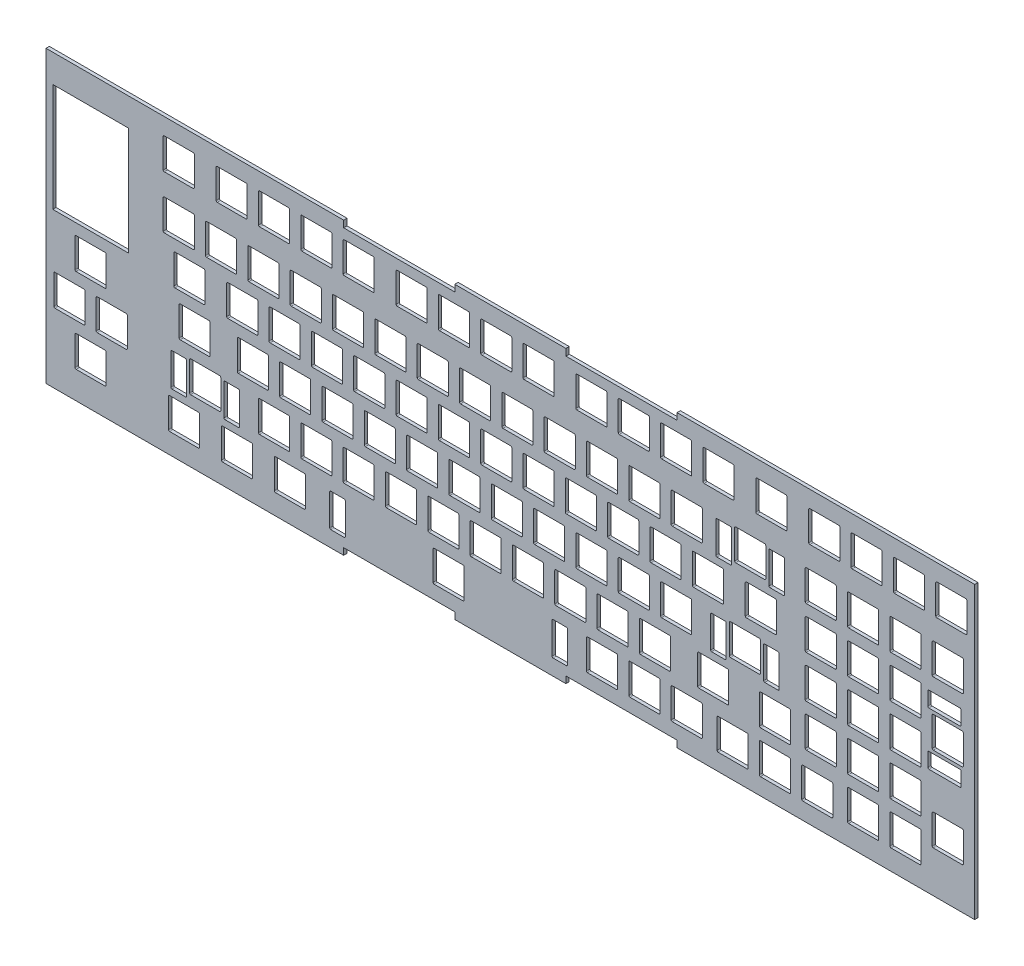
SolidWorks part; units mm, degrees
ref_plane "Přední rovina" through (0, 0, 0) normal (0, 0, 1) x (1, 0, 0)
ref_plane "Horní rovina" through (0, 0, 0) normal (0, 1, 0) x (1, 0, 0)
ref_plane "Pravá rovina" through (0, 0, 0) normal (1, 0, 0) x (0, 0, -1)
sketch "Model" plane through (0, 0, 0) normal (0, 0, 1) x (1, 0, 0)
  line L0 (53.8256, -2.525) -> (66.8256, -2.525)
  line L1 (53.8256, -16.525) -> (66.8256, -16.525)
  line L2 (53.3256, -3.025) -> (53.3256, -16.025)
  line L3 (67.3256, -3.025) -> (67.3256, -16.025)
  line L4 (77.6381, -2.525) -> (90.6381, -2.525)
  line L5 (77.6381, -16.525) -> (90.6381, -16.525)
  line L6 (77.1381, -3.025) -> (77.1381, -16.025)
  line L7 (91.1381, -3.025) -> (91.1381, -16.025)
  line L8 (96.6881, -2.525) -> (109.6881, -2.525)
  line L9 (96.6881, -16.525) -> (109.6881, -16.525)
  line L10 (96.1881, -3.025) -> (96.1881, -16.025)
  line L11 (110.1881, -3.025) -> (110.1881, -16.025)
  line L12 (115.7381, -2.525) -> (128.7381, -2.525)
  line L13 (115.7381, -16.525) -> (128.7381, -16.525)
  line L14 (115.2381, -3.025) -> (115.2381, -16.025)
  line L15 (129.2381, -3.025) -> (129.2381, -16.025)
  line L16 (134.7881, -2.525) -> (147.7881, -2.525)
  line L17 (134.7881, -16.525) -> (147.7881, -16.525)
  line L18 (134.2881, -3.025) -> (134.2881, -16.025)
  line L19 (148.2881, -3.025) -> (148.2881, -16.025)
  line L20 (158.6006, -2.525) -> (171.6006, -2.525)
  line L21 (158.6006, -16.525) -> (171.6006, -16.525)
  line L22 (158.1006, -3.025) -> (158.1006, -16.025)
  line L23 (172.1006, -3.025) -> (172.1006, -16.025)
  line L24 (177.6506, -2.525) -> (190.6506, -2.525)
  line L25 (177.6506, -16.525) -> (190.6506, -16.525)
  line L26 (177.1506, -3.025) -> (177.1506, -16.025)
  line L27 (191.1506, -3.025) -> (191.1506, -16.025)
  line L28 (196.7006, -2.525) -> (209.7006, -2.525)
  line L29 (196.7006, -16.525) -> (209.7006, -16.525)
  line L30 (196.2006, -3.025) -> (196.2006, -16.025)
  line L31 (210.2006, -3.025) -> (210.2006, -16.025)
  line L32 (215.7506, -2.525) -> (228.7506, -2.525)
  line L33 (215.7506, -16.525) -> (228.7506, -16.525)
  line L34 (215.2506, -3.025) -> (215.2506, -16.025)
  line L35 (229.2506, -3.025) -> (229.2506, -16.025)
  line L36 (239.5631, -2.525) -> (252.5631, -2.525)
  line L37 (239.5631, -16.525) -> (252.5631, -16.525)
  line L38 (239.0631, -3.025) -> (239.0631, -16.025)
  line L39 (253.0631, -3.025) -> (253.0631, -16.025)
  line L40 (258.6131, -2.525) -> (271.6131, -2.525)
  line L41 (258.6131, -16.525) -> (271.6131, -16.525)
  line L42 (258.1131, -3.025) -> (258.1131, -16.025)
  line L43 (272.1131, -3.025) -> (272.1131, -16.025)
  line L44 (277.6631, -2.525) -> (290.6631, -2.525)
  line L45 (277.6631, -16.525) -> (290.6631, -16.525)
  line L46 (277.1631, -3.025) -> (277.1631, -16.025)
  line L47 (291.1631, -3.025) -> (291.1631, -16.025)
  line L48 (296.7131, -2.525) -> (309.7131, -2.525)
  line L49 (296.7131, -16.525) -> (309.7131, -16.525)
  line L50 (296.2131, -3.025) -> (296.2131, -16.025)
  line L51 (310.2131, -3.025) -> (310.2131, -16.025)
  line L52 (320.5256, -2.525) -> (333.5256, -2.525)
  line L53 (320.5256, -16.525) -> (333.5256, -16.525)
  line L54 (320.0256, -3.025) -> (320.0256, -16.025)
  line L55 (334.0256, -3.025) -> (334.0256, -16.025)
  line L56 (344.3381, -2.525) -> (357.3381, -2.525)
  line L57 (344.3381, -16.525) -> (357.3381, -16.525)
  line L58 (343.8381, -3.025) -> (343.8381, -16.025)
  line L59 (357.8381, -3.025) -> (357.8381, -16.025)
  line L60 (363.3881, -2.525) -> (376.3881, -2.525)
  line L61 (363.3881, -16.525) -> (376.3881, -16.525)
  line L62 (362.8881, -3.025) -> (362.8881, -16.025)
  line L63 (376.8881, -3.025) -> (376.8881, -16.025)
  line L64 (382.4381, -2.525) -> (395.4381, -2.525)
  line L65 (382.4381, -16.525) -> (395.4381, -16.525)
  line L66 (381.9381, -3.025) -> (381.9381, -16.025)
  line L67 (395.9381, -3.025) -> (395.9381, -16.025)
  line L68 (401.4881, -2.525) -> (414.4881, -2.525)
  line L69 (401.4881, -16.525) -> (414.4881, -16.525)
  line L70 (400.9881, -3.025) -> (400.9881, -16.025)
  line L71 (414.9881, -3.025) -> (414.9881, -16.025)
  line L72 (53.8256, -26.3375) -> (66.8256, -26.3375)
  line L73 (53.8256, -40.3375) -> (66.8256, -40.3375)
  line L74 (53.3256, -26.8375) -> (53.3256, -39.8375)
  line L75 (67.3256, -26.8375) -> (67.3256, -39.8375)
  line L76 (72.8756, -26.3375) -> (85.8756, -26.3375)
  line L77 (72.8756, -40.3375) -> (85.8756, -40.3375)
  line L78 (72.3756, -26.8375) -> (72.3756, -39.8375)
  line L79 (86.3756, -26.8375) -> (86.3756, -39.8375)
  line L80 (91.9256, -26.3375) -> (104.9256, -26.3375)
  line L81 (91.9256, -40.3375) -> (104.9256, -40.3375)
  line L82 (91.4256, -26.8375) -> (91.4256, -39.8375)
  line L83 (105.4256, -26.8375) -> (105.4256, -39.8375)
  line L84 (110.9756, -26.3375) -> (123.9756, -26.3375)
  line L85 (110.9756, -40.3375) -> (123.9756, -40.3375)
  line L86 (110.4756, -26.8375) -> (110.4756, -39.8375)
  line L87 (124.4756, -26.8375) -> (124.4756, -39.8375)
  line L88 (130.0256, -26.3375) -> (143.0256, -26.3375)
  line L89 (130.0256, -40.3375) -> (143.0256, -40.3375)
  line L90 (129.5256, -26.8375) -> (129.5256, -39.8375)
  line L91 (143.5256, -26.8375) -> (143.5256, -39.8375)
  line L92 (149.0756, -26.3375) -> (162.0756, -26.3375)
  line L93 (149.0756, -40.3375) -> (162.0756, -40.3375)
  line L94 (148.5756, -26.8375) -> (148.5756, -39.8375)
  line L95 (162.5756, -26.8375) -> (162.5756, -39.8375)
  line L96 (168.1256, -26.3375) -> (181.1256, -26.3375)
  line L97 (168.1256, -40.3375) -> (181.1256, -40.3375)
  line L98 (167.6256, -26.8375) -> (167.6256, -39.8375)
  line L99 (181.6256, -26.8375) -> (181.6256, -39.8375)
  line L100 (187.1756, -26.3375) -> (200.1756, -26.3375)
  line L101 (187.1756, -40.3375) -> (200.1756, -40.3375)
  line L102 (186.6756, -26.8375) -> (186.6756, -39.8375)
  line L103 (200.6756, -26.8375) -> (200.6756, -39.8375)
  line L104 (206.2256, -26.3375) -> (219.2256, -26.3375)
  line L105 (206.2256, -40.3375) -> (219.2256, -40.3375)
  line L106 (205.7256, -26.8375) -> (205.7256, -39.8375)
  line L107 (219.7256, -26.8375) -> (219.7256, -39.8375)
  line L108 (225.2756, -26.3375) -> (238.2756, -26.3375)
  line L109 (225.2756, -40.3375) -> (238.2756, -40.3375)
  line L110 (224.7756, -26.8375) -> (224.7756, -39.8375)
  line L111 (238.7756, -26.8375) -> (238.7756, -39.8375)
  line L112 (244.3256, -26.3375) -> (257.3256, -26.3375)
  line L113 (244.3256, -40.3375) -> (257.3256, -40.3375)
  line L114 (243.8256, -26.8375) -> (243.8256, -39.8375)
  line L115 (257.8256, -26.8375) -> (257.8256, -39.8375)
  line L116 (263.3756, -26.3375) -> (276.3756, -26.3375)
  line L117 (263.3756, -40.3375) -> (276.3756, -40.3375)
  line L118 (262.8756, -26.8375) -> (262.8756, -39.8375)
  line L119 (276.8756, -26.8375) -> (276.8756, -39.8375)
  line L120 (282.4256, -26.3375) -> (295.4256, -26.3375)
  line L121 (282.4256, -40.3375) -> (295.4256, -40.3375)
  line L122 (281.9256, -26.8375) -> (281.9256, -39.8375)
  line L123 (295.9256, -26.8375) -> (295.9256, -39.8375)
  line L124 (311.0006, -26.3375) -> (324.0006, -26.3375)
  line L125 (311.0006, -40.3375) -> (324.0006, -40.3375)
  line L126 (310.5006, -26.8375) -> (310.5006, -39.8375)
  line L127 (324.5006, -26.8375) -> (324.5006, -39.8375)
  line L128 (302.5626, -27.3375) -> (308.5626, -27.3375)
  line L129 (302.5626, -42.3375) -> (308.5626, -42.3375)
  line L130 (302.0626, -27.8375) -> (302.0626, -41.8375)
  line L131 (309.0626, -27.8375) -> (309.0626, -41.8375)
  line L132 (326.4386, -27.3375) -> (332.4386, -27.3375)
  line L133 (326.4386, -42.3375) -> (332.4386, -42.3375)
  line L134 (325.9386, -27.8375) -> (325.9386, -41.8375)
  line L135 (332.9386, -27.8375) -> (332.9386, -41.8375)
  line L136 (342.7513, -26.3375) -> (355.7513, -26.3375)
  line L137 (342.7513, -40.3375) -> (355.7513, -40.3375)
  line L138 (342.2513, -26.8375) -> (342.2513, -39.8375)
  line L139 (356.2513, -26.8375) -> (356.2513, -39.8375)
  line L140 (361.8013, -26.3375) -> (374.8013, -26.3375)
  line L141 (361.8013, -40.3375) -> (374.8013, -40.3375)
  line L142 (361.3013, -26.8375) -> (361.3013, -39.8375)
  line L143 (375.3013, -26.8375) -> (375.3013, -39.8375)
  line L144 (380.8513, -26.3375) -> (393.8513, -26.3375)
  line L145 (380.8513, -40.3375) -> (393.8513, -40.3375)
  line L146 (380.3513, -26.8375) -> (380.3513, -39.8375)
  line L147 (394.3513, -26.8375) -> (394.3513, -39.8375)
  line L148 (399.9013, -26.3375) -> (412.9013, -26.3375)
  line L149 (399.9013, -40.3375) -> (412.9013, -40.3375)
  line L150 (399.4013, -26.8375) -> (399.4013, -39.8375)
  line L151 (413.4013, -26.8375) -> (413.4013, -39.8375)
  line L152 (58.5881, -45.3875) -> (71.5881, -45.3875)
  line L153 (58.5881, -59.3875) -> (71.5881, -59.3875)
  line L154 (58.0881, -45.8875) -> (58.0881, -58.8875)
  line L155 (72.0881, -45.8875) -> (72.0881, -58.8875)
  line L156 (82.4006, -45.3875) -> (95.4006, -45.3875)
  line L157 (82.4006, -59.3875) -> (95.4006, -59.3875)
  line L158 (81.9006, -45.8875) -> (81.9006, -58.8875)
  line L159 (95.9006, -45.8875) -> (95.9006, -58.8875)
  line L160 (101.4506, -45.3875) -> (114.4506, -45.3875)
  line L161 (101.4506, -59.3875) -> (114.4506, -59.3875)
  line L162 (100.9506, -45.8875) -> (100.9506, -58.8875)
  line L163 (114.9506, -45.8875) -> (114.9506, -58.8875)
  line L164 (120.5006, -45.3875) -> (133.5006, -45.3875)
  line L165 (120.5006, -59.3875) -> (133.5006, -59.3875)
  line L166 (120.0006, -45.8875) -> (120.0006, -58.8875)
  line L167 (134.0006, -45.8875) -> (134.0006, -58.8875)
  line L168 (139.5506, -45.3875) -> (152.5506, -45.3875)
  line L169 (139.5506, -59.3875) -> (152.5506, -59.3875)
  line L170 (139.0506, -45.8875) -> (139.0506, -58.8875)
  line L171 (153.0506, -45.8875) -> (153.0506, -58.8875)
  line L172 (158.6006, -45.3875) -> (171.6006, -45.3875)
  line L173 (158.6006, -59.3875) -> (171.6006, -59.3875)
  line L174 (158.1006, -45.8875) -> (158.1006, -58.8875)
  line L175 (172.1006, -45.8875) -> (172.1006, -58.8875)
  line L176 (177.6506, -45.3875) -> (190.6506, -45.3875)
  line L177 (177.6506, -59.3875) -> (190.6506, -59.3875)
  line L178 (177.1506, -45.8875) -> (177.1506, -58.8875)
  line L179 (191.1506, -45.8875) -> (191.1506, -58.8875)
  line L180 (196.7006, -45.3875) -> (209.7006, -45.3875)
  line L181 (196.7006, -59.3875) -> (209.7006, -59.3875)
  line L182 (196.2006, -45.8875) -> (196.2006, -58.8875)
  line L183 (210.2006, -45.8875) -> (210.2006, -58.8875)
  line L184 (215.7506, -45.3875) -> (228.7506, -45.3875)
  line L185 (215.7506, -59.3875) -> (228.7506, -59.3875)
  line L186 (215.2506, -45.8875) -> (215.2506, -58.8875)
  line L187 (229.2506, -45.8875) -> (229.2506, -58.8875)
  line L188 (234.8006, -45.3875) -> (247.8006, -45.3875)
  line L189 (234.8006, -59.3875) -> (247.8006, -59.3875)
  line L190 (234.3006, -45.8875) -> (234.3006, -58.8875)
  line L191 (248.3006, -45.8875) -> (248.3006, -58.8875)
  line L192 (253.8506, -45.3875) -> (266.8506, -45.3875)
  line L193 (253.8506, -59.3875) -> (266.8506, -59.3875)
  line L194 (253.3506, -45.8875) -> (253.3506, -58.8875)
  line L195 (267.3506, -45.8875) -> (267.3506, -58.8875)
  line L196 (272.9006, -45.3875) -> (285.9006, -45.3875)
  line L197 (272.9006, -59.3875) -> (285.9006, -59.3875)
  line L198 (272.4006, -45.8875) -> (272.4006, -58.8875)
  line L199 (286.4006, -45.8875) -> (286.4006, -58.8875)
  line L200 (291.9506, -45.3875) -> (304.9506, -45.3875)
  line L201 (291.9506, -59.3875) -> (304.9506, -59.3875)
  line L202 (291.4506, -45.8875) -> (291.4506, -58.8875)
  line L203 (305.4506, -45.8875) -> (305.4506, -58.8875)
  line L204 (315.7631, -45.3875) -> (328.7631, -45.3875)
  line L205 (315.7631, -59.3875) -> (328.7631, -59.3875)
  line L206 (315.2631, -45.8875) -> (315.2631, -58.8875)
  line L207 (329.2631, -45.8875) -> (329.2631, -58.8875)
  line L208 (342.7513, -45.3875) -> (355.7513, -45.3875)
  line L209 (342.7513, -59.3875) -> (355.7513, -59.3875)
  line L210 (342.2513, -45.8875) -> (342.2513, -58.8875)
  line L211 (356.2513, -45.8875) -> (356.2513, -58.8875)
  line L212 (361.8013, -45.3875) -> (374.8013, -45.3875)
  line L213 (361.8013, -59.3875) -> (374.8013, -59.3875)
  line L214 (361.3013, -45.8875) -> (361.3013, -58.8875)
  line L215 (375.3013, -45.8875) -> (375.3013, -58.8875)
  line L216 (380.8513, -45.3875) -> (393.8513, -45.3875)
  line L217 (380.8513, -59.3875) -> (393.8513, -59.3875)
  line L218 (380.3513, -45.8875) -> (380.3513, -58.8875)
  line L219 (394.3513, -45.8875) -> (394.3513, -58.8875)
  line L220 (413.4013, -55.4125) -> (413.4013, -68.4125)
  line L221 (399.4013, -55.4125) -> (399.4013, -68.4125)
  line L222 (412.9013, -54.9125) -> (399.9013, -54.9125)
  line L223 (412.9013, -68.9125) -> (399.9013, -68.9125)
  line L224 (412.4013, -46.9745) -> (412.4013, -52.9745)
  line L225 (397.4013, -46.9745) -> (397.4013, -52.9745)
  line L226 (411.9013, -46.4745) -> (397.9013, -46.4745)
  line L227 (411.9013, -53.4745) -> (397.9013, -53.4745)
  line L228 (412.4013, -70.8505) -> (412.4013, -76.8505)
  line L229 (397.4013, -70.8505) -> (397.4013, -76.8505)
  line L230 (411.9013, -70.3505) -> (397.9013, -70.3505)
  line L231 (411.9013, -77.3505) -> (397.9013, -77.3505)
  line L232 (14.1369, -61.2619) -> (27.1369, -61.2619)
  line L233 (14.1369, -75.2619) -> (27.1369, -75.2619)
  line L234 (13.6369, -61.7619) -> (13.6369, -74.7619)
  line L235 (27.6369, -61.7619) -> (27.6369, -74.7619)
  line L236 (60.9694, -64.4375) -> (73.9694, -64.4375)
  line L237 (60.9694, -78.4375) -> (73.9694, -78.4375)
  line L238 (60.4694, -64.9375) -> (60.4694, -77.9375)
  line L239 (74.4694, -64.9375) -> (74.4694, -77.9375)
  line L240 (87.1631, -64.4375) -> (100.1631, -64.4375)
  line L241 (87.1631, -78.4375) -> (100.1631, -78.4375)
  line L242 (86.6631, -64.9375) -> (86.6631, -77.9375)
  line L243 (100.6631, -64.9375) -> (100.6631, -77.9375)
  line L244 (106.2131, -64.4375) -> (119.2131, -64.4375)
  line L245 (106.2131, -78.4375) -> (119.2131, -78.4375)
  line L246 (105.7131, -64.9375) -> (105.7131, -77.9375)
  line L247 (119.7131, -64.9375) -> (119.7131, -77.9375)
  line L248 (125.2631, -64.4375) -> (138.2631, -64.4375)
  line L249 (125.2631, -78.4375) -> (138.2631, -78.4375)
  line L250 (124.7631, -64.9375) -> (124.7631, -77.9375)
  line L251 (138.7631, -64.9375) -> (138.7631, -77.9375)
  line L252 (144.3131, -64.4375) -> (157.3131, -64.4375)
  line L253 (144.3131, -78.4375) -> (157.3131, -78.4375)
  line L254 (143.8131, -64.9375) -> (143.8131, -77.9375)
  line L255 (157.8131, -64.9375) -> (157.8131, -77.9375)
  line L256 (163.3631, -64.4375) -> (176.3631, -64.4375)
  line L257 (163.3631, -78.4375) -> (176.3631, -78.4375)
  line L258 (162.8631, -64.9375) -> (162.8631, -77.9375)
  line L259 (176.8631, -64.9375) -> (176.8631, -77.9375)
  line L260 (182.4131, -64.4375) -> (195.4131, -64.4375)
  line L261 (182.4131, -78.4375) -> (195.4131, -78.4375)
  line L262 (181.9131, -64.9375) -> (181.9131, -77.9375)
  line L263 (195.9131, -64.9375) -> (195.9131, -77.9375)
  line L264 (201.4631, -64.4375) -> (214.4631, -64.4375)
  line L265 (201.4631, -78.4375) -> (214.4631, -78.4375)
  line L266 (200.9631, -64.9375) -> (200.9631, -77.9375)
  line L267 (214.9631, -64.9375) -> (214.9631, -77.9375)
  line L268 (220.5131, -64.4375) -> (233.5131, -64.4375)
  line L269 (220.5131, -78.4375) -> (233.5131, -78.4375)
  line L270 (220.0131, -64.9375) -> (220.0131, -77.9375)
  line L271 (234.0131, -64.9375) -> (234.0131, -77.9375)
  line L272 (239.5631, -64.4375) -> (252.5631, -64.4375)
  line L273 (239.5631, -78.4375) -> (252.5631, -78.4375)
  line L274 (239.0631, -64.9375) -> (239.0631, -77.9375)
  line L275 (253.0631, -64.9375) -> (253.0631, -77.9375)
  line L276 (258.6131, -64.4375) -> (271.6131, -64.4375)
  line L277 (258.6131, -78.4375) -> (271.6131, -78.4375)
  line L278 (258.1131, -64.9375) -> (258.1131, -77.9375)
  line L279 (272.1131, -64.9375) -> (272.1131, -77.9375)
  line L280 (277.6631, -64.4375) -> (290.6631, -64.4375)
  line L281 (277.6631, -78.4375) -> (290.6631, -78.4375)
  line L282 (277.1631, -64.9375) -> (277.1631, -77.9375)
  line L283 (291.1631, -64.9375) -> (291.1631, -77.9375)
  line L284 (308.6194, -64.4375) -> (321.6194, -64.4375)
  line L285 (308.6194, -78.4375) -> (321.6194, -78.4375)
  line L286 (308.1194, -64.9375) -> (308.1194, -77.9375)
  line L287 (322.1194, -64.9375) -> (322.1194, -77.9375)
  line L288 (300.1814, -65.4375) -> (306.1814, -65.4375)
  line L289 (300.1814, -80.4375) -> (306.1814, -80.4375)
  line L290 (299.6814, -65.9375) -> (299.6814, -79.9375)
  line L291 (306.6814, -65.9375) -> (306.6814, -79.9375)
  line L292 (324.0574, -65.4375) -> (330.0574, -65.4375)
  line L293 (324.0574, -80.4375) -> (330.0574, -80.4375)
  line L294 (323.5574, -65.9375) -> (323.5574, -79.9375)
  line L295 (330.5574, -65.9375) -> (330.5574, -79.9375)
  line L296 (342.7513, -64.4375) -> (355.7513, -64.4375)
  line L297 (342.7513, -78.4375) -> (355.7513, -78.4375)
  line L298 (342.2513, -64.9375) -> (342.2513, -77.9375)
  line L299 (356.2513, -64.9375) -> (356.2513, -77.9375)
  line L300 (361.8013, -64.4375) -> (374.8013, -64.4375)
  line L301 (361.8013, -78.4375) -> (374.8013, -78.4375)
  line L302 (361.3013, -64.9375) -> (361.3013, -77.9375)
  line L303 (375.3013, -64.9375) -> (375.3013, -77.9375)
  line L304 (380.8513, -64.4375) -> (393.8513, -64.4375)
  line L305 (380.8513, -78.4375) -> (393.8513, -78.4375)
  line L306 (380.3513, -64.9375) -> (380.3513, -77.9375)
  line L307 (394.3513, -64.9375) -> (394.3513, -77.9375)
  line L308 (4.6119, -80.3119) -> (17.6119, -80.3119)
  line L309 (4.6119, -94.3119) -> (17.6119, -94.3119)
  line L310 (4.1119, -80.8119) -> (4.1119, -93.8119)
  line L311 (18.1119, -80.8119) -> (18.1119, -93.8119)
  line L312 (23.6619, -80.3119) -> (36.6619, -80.3119)
  line L313 (23.6619, -94.3119) -> (36.6619, -94.3119)
  line L314 (23.1619, -80.8119) -> (23.1619, -93.8119)
  line L315 (37.1619, -80.8119) -> (37.1619, -93.8119)
  line L316 (65.7319, -83.4875) -> (78.7319, -83.4875)
  line L317 (65.7319, -97.4875) -> (78.7319, -97.4875)
  line L318 (65.2319, -83.9875) -> (65.2319, -96.9875)
  line L319 (79.2319, -83.9875) -> (79.2319, -96.9875)
  line L320 (57.2939, -84.4875) -> (63.2939, -84.4875)
  line L321 (57.2939, -99.4875) -> (63.2939, -99.4875)
  line L322 (56.7939, -84.9875) -> (56.7939, -98.9875)
  line L323 (63.7939, -84.9875) -> (63.7939, -98.9875)
  line L324 (81.1699, -84.4875) -> (87.1699, -84.4875)
  line L325 (81.1699, -99.4875) -> (87.1699, -99.4875)
  line L326 (80.6699, -84.9875) -> (80.6699, -98.9875)
  line L327 (87.6699, -84.9875) -> (87.6699, -98.9875)
  line L328 (96.6881, -83.4875) -> (109.6881, -83.4875)
  line L329 (96.6881, -97.4875) -> (109.6881, -97.4875)
  line L330 (96.1881, -83.9875) -> (96.1881, -96.9875)
  line L331 (110.1881, -83.9875) -> (110.1881, -96.9875)
  line L332 (115.7381, -83.4875) -> (128.7381, -83.4875)
  line L333 (115.7381, -97.4875) -> (128.7381, -97.4875)
  line L334 (115.2381, -83.9875) -> (115.2381, -96.9875)
  line L335 (129.2381, -83.9875) -> (129.2381, -96.9875)
  line L336 (134.7881, -83.4875) -> (147.7881, -83.4875)
  line L337 (134.7881, -97.4875) -> (147.7881, -97.4875)
  line L338 (134.2881, -83.9875) -> (134.2881, -96.9875)
  line L339 (148.2881, -83.9875) -> (148.2881, -96.9875)
  line L340 (153.8381, -83.4875) -> (166.8381, -83.4875)
  line L341 (153.8381, -97.4875) -> (166.8381, -97.4875)
  line L342 (153.3381, -83.9875) -> (153.3381, -96.9875)
  line L343 (167.3381, -83.9875) -> (167.3381, -96.9875)
  line L344 (172.8881, -83.4875) -> (185.8881, -83.4875)
  line L345 (172.8881, -97.4875) -> (185.8881, -97.4875)
  line L346 (172.3881, -83.9875) -> (172.3881, -96.9875)
  line L347 (186.3881, -83.9875) -> (186.3881, -96.9875)
  line L348 (191.9381, -83.4875) -> (204.9381, -83.4875)
  line L349 (191.9381, -97.4875) -> (204.9381, -97.4875)
  line L350 (191.4381, -83.9875) -> (191.4381, -96.9875)
  line L351 (205.4381, -83.9875) -> (205.4381, -96.9875)
  line L352 (210.9881, -83.4875) -> (223.9881, -83.4875)
  line L353 (210.9881, -97.4875) -> (223.9881, -97.4875)
  line L354 (210.4881, -83.9875) -> (210.4881, -96.9875)
  line L355 (224.4881, -83.9875) -> (224.4881, -96.9875)
  line L356 (230.0381, -83.4875) -> (243.0381, -83.4875)
  line L357 (230.0381, -97.4875) -> (243.0381, -97.4875)
  line L358 (229.5381, -83.9875) -> (229.5381, -96.9875)
  line L359 (243.5381, -83.9875) -> (243.5381, -96.9875)
  line L360 (249.0881, -83.4875) -> (262.0881, -83.4875)
  line L361 (249.0881, -97.4875) -> (262.0881, -97.4875)
  line L362 (248.5881, -83.9875) -> (248.5881, -96.9875)
  line L363 (262.5881, -83.9875) -> (262.5881, -96.9875)
  line L364 (268.1381, -83.4875) -> (281.1381, -83.4875)
  line L365 (268.1381, -97.4875) -> (281.1381, -97.4875)
  line L366 (267.6381, -83.9875) -> (267.6381, -96.9875)
  line L367 (281.6381, -83.9875) -> (281.6381, -96.9875)
  line L368 (294.3319, -83.4875) -> (307.3319, -83.4875)
  line L369 (294.3319, -97.4875) -> (307.3319, -97.4875)
  line L370 (293.8319, -83.9875) -> (293.8319, -96.9875)
  line L371 (307.8319, -83.9875) -> (307.8319, -96.9875)
  line L372 (342.7513, -83.4875) -> (355.7513, -83.4875)
  line L373 (342.7513, -97.4875) -> (355.7513, -97.4875)
  line L374 (342.2513, -83.9875) -> (342.2513, -96.9875)
  line L375 (356.2513, -83.9875) -> (356.2513, -96.9875)
  line L376 (361.8013, -83.4875) -> (374.8013, -83.4875)
  line L377 (361.8013, -97.4875) -> (374.8013, -97.4875)
  line L378 (361.3013, -83.9875) -> (361.3013, -96.9875)
  line L379 (375.3013, -83.9875) -> (375.3013, -96.9875)
  line L380 (380.8513, -83.4875) -> (393.8513, -83.4875)
  line L381 (380.8513, -97.4875) -> (393.8513, -97.4875)
  line L382 (380.3513, -83.9875) -> (380.3513, -96.9875)
  line L383 (394.3513, -83.9875) -> (394.3513, -96.9875)
  line L384 (413.4013, -93.5125) -> (413.4013, -106.5125)
  line L385 (399.4013, -93.5125) -> (399.4013, -106.5125)
  line L386 (412.9013, -93.0125) -> (399.9013, -93.0125)
  line L387 (412.9013, -107.0125) -> (399.9013, -107.0125)
  line L396 (322.1125, -85.0744) -> (335.1125, -85.0744)
  line L397 (322.1125, -99.0744) -> (335.1125, -99.0744)
  line L398 (321.6125, -85.5744) -> (321.6125, -98.5744)
  line L399 (335.6125, -85.5744) -> (335.6125, -98.5744)
  line L400 (14.1369, -99.3619) -> (27.1369, -99.3619)
  line L401 (14.1369, -113.3619) -> (27.1369, -113.3619)
  line L402 (13.6369, -99.8619) -> (13.6369, -112.8619)
  line L403 (27.6369, -99.8619) -> (27.6369, -112.8619)
  line L404 (56.2069, -102.5375) -> (69.2069, -102.5375)
  line L405 (56.2069, -116.5375) -> (69.2069, -116.5375)
  line L406 (55.7069, -103.0375) -> (55.7069, -116.0375)
  line L407 (69.7069, -103.0375) -> (69.7069, -116.0375)
  line L408 (80.0194, -102.5375) -> (93.0194, -102.5375)
  line L409 (80.0194, -116.5375) -> (93.0194, -116.5375)
  line L410 (79.5194, -103.0375) -> (79.5194, -116.0375)
  line L411 (93.5194, -103.0375) -> (93.5194, -116.0375)
  line L412 (103.8319, -102.5375) -> (116.8319, -102.5375)
  line L413 (103.8319, -116.5375) -> (116.8319, -116.5375)
  line L414 (103.3319, -103.0375) -> (103.3319, -116.0375)
  line L415 (117.3319, -103.0375) -> (117.3319, -116.0375)
  line L416 (175.2694, -102.5375) -> (188.2694, -102.5375)
  line L417 (175.2694, -116.5375) -> (188.2694, -116.5375)
  line L418 (174.7694, -103.0375) -> (174.7694, -116.0375)
  line L419 (188.7694, -103.0375) -> (188.7694, -116.0375)
  line L420 (128.7694, -103.5375) -> (134.7694, -103.5375)
  line L421 (128.7694, -118.5375) -> (134.7694, -118.5375)
  line L422 (128.2694, -104.0375) -> (128.2694, -118.0375)
  line L423 (135.2694, -104.0375) -> (135.2694, -118.0375)
  line L424 (228.7694, -103.5375) -> (234.7694, -103.5375)
  line L425 (228.7694, -118.5375) -> (234.7694, -118.5375)
  line L426 (228.2694, -104.0375) -> (228.2694, -118.0375)
  line L427 (235.2694, -104.0375) -> (235.2694, -118.0375)
  line L428 (244.3256, -102.5375) -> (257.3256, -102.5375)
  line L429 (244.3256, -116.5375) -> (257.3256, -116.5375)
  line L430 (243.8256, -103.0375) -> (243.8256, -116.0375)
  line L431 (257.8256, -103.0375) -> (257.8256, -116.0375)
  line L432 (263.3756, -102.5375) -> (276.3756, -102.5375)
  line L433 (263.3756, -116.5375) -> (276.3756, -116.5375)
  line L434 (262.8756, -103.0375) -> (262.8756, -116.0375)
  line L435 (276.8756, -103.0375) -> (276.8756, -116.0375)
  line L436 (282.4256, -102.5375) -> (295.4256, -102.5375)
  line L437 (282.4256, -116.5375) -> (295.4256, -116.5375)
  line L438 (281.9256, -103.0375) -> (281.9256, -116.0375)
  line L439 (295.9256, -103.0375) -> (295.9256, -116.0375)
  line L440 (361.8013, -102.5375) -> (374.8013, -102.5375)
  line L441 (361.8013, -116.5375) -> (374.8013, -116.5375)
  line L442 (361.3013, -103.0375) -> (361.3013, -116.0375)
  line L443 (375.3013, -103.0375) -> (375.3013, -116.0375)
  line L444 (380.8513, -102.5375) -> (393.8513, -102.5375)
  line L445 (380.8513, -116.5375) -> (393.8513, -116.5375)
  line L446 (380.3513, -103.0375) -> (380.3513, -116.0375)
  line L447 (394.3513, -103.0375) -> (394.3513, -116.0375)
  line L448 (303.0625, -104.1244) -> (316.0625, -104.1244)
  line L449 (303.0625, -118.1244) -> (316.0625, -118.1244)
  line L450 (302.5625, -104.6244) -> (302.5625, -117.6244)
  line L451 (316.5625, -104.6244) -> (316.5625, -117.6244)
  line L452 (322.1125, -104.1244) -> (335.1125, -104.1244)
  line L453 (322.1125, -118.1244) -> (335.1125, -118.1244)
  line L454 (321.6125, -104.6244) -> (321.6125, -117.6244)
  line L455 (335.6125, -104.6244) -> (335.6125, -117.6244)
  line L456 (341.1625, -104.1244) -> (354.1625, -104.1244)
  line L457 (341.1625, -118.1244) -> (354.1625, -118.1244)
  line L458 (340.6625, -104.6244) -> (340.6625, -117.6244)
  line L459 (354.6625, -104.6244) -> (354.6625, -117.6244)
  line L460 (1.5869, -120.6494) -> (417.5131, -120.6494)
  line L461 (1.5869, 0) -> (417.5131, 0)
  line L462 (1.5869, -120.6494) -> (1.5869, 0)
  line L463 (417.5131, -120.6494) -> (417.5131, 0)
  arc A0 (53.8256, -2.525) -> (53.3256, -3.025) centre (53.8256, -3.025) ccw
  arc A1 (67.3256, -3.025) -> (66.8256, -2.525) centre (66.8256, -3.025) ccw
  arc A2 (53.3256, -16.025) -> (53.8256, -16.525) centre (53.8256, -16.025) ccw
  arc A3 (66.8256, -16.525) -> (67.3256, -16.025) centre (66.8256, -16.025) ccw
  arc A4 (77.6381, -2.525) -> (77.1381, -3.025) centre (77.6381, -3.025) ccw
  arc A5 (91.1381, -3.025) -> (90.6381, -2.525) centre (90.6381, -3.025) ccw
  arc A6 (77.1381, -16.025) -> (77.6381, -16.525) centre (77.6381, -16.025) ccw
  arc A7 (90.6381, -16.525) -> (91.1381, -16.025) centre (90.6381, -16.025) ccw
  arc A8 (96.6881, -2.525) -> (96.1881, -3.025) centre (96.6881, -3.025) ccw
  arc A9 (110.1881, -3.025) -> (109.6881, -2.525) centre (109.6881, -3.025) ccw
  arc A10 (96.1881, -16.025) -> (96.6881, -16.525) centre (96.6881, -16.025) ccw
  arc A11 (109.6881, -16.525) -> (110.1881, -16.025) centre (109.6881, -16.025) ccw
  arc A12 (115.7381, -2.525) -> (115.2381, -3.025) centre (115.7381, -3.025) ccw
  arc A13 (129.2381, -3.025) -> (128.7381, -2.525) centre (128.7381, -3.025) ccw
  arc A14 (115.2381, -16.025) -> (115.7381, -16.525) centre (115.7381, -16.025) ccw
  arc A15 (128.7381, -16.525) -> (129.2381, -16.025) centre (128.7381, -16.025) ccw
  arc A16 (134.7881, -2.525) -> (134.2881, -3.025) centre (134.7881, -3.025) ccw
  arc A17 (148.2881, -3.025) -> (147.7881, -2.525) centre (147.7881, -3.025) ccw
  arc A18 (134.2881, -16.025) -> (134.7881, -16.525) centre (134.7881, -16.025) ccw
  arc A19 (147.7881, -16.525) -> (148.2881, -16.025) centre (147.7881, -16.025) ccw
  arc A20 (158.6006, -2.525) -> (158.1006, -3.025) centre (158.6006, -3.025) ccw
  arc A21 (172.1006, -3.025) -> (171.6006, -2.525) centre (171.6006, -3.025) ccw
  arc A22 (158.1006, -16.025) -> (158.6006, -16.525) centre (158.6006, -16.025) ccw
  arc A23 (171.6006, -16.525) -> (172.1006, -16.025) centre (171.6006, -16.025) ccw
  arc A24 (177.6506, -2.525) -> (177.1506, -3.025) centre (177.6506, -3.025) ccw
  arc A25 (191.1506, -3.025) -> (190.6506, -2.525) centre (190.6506, -3.025) ccw
  arc A26 (177.1506, -16.025) -> (177.6506, -16.525) centre (177.6506, -16.025) ccw
  arc A27 (190.6506, -16.525) -> (191.1506, -16.025) centre (190.6506, -16.025) ccw
  arc A28 (196.7006, -2.525) -> (196.2006, -3.025) centre (196.7006, -3.025) ccw
  arc A29 (210.2006, -3.025) -> (209.7006, -2.525) centre (209.7006, -3.025) ccw
  arc A30 (196.2006, -16.025) -> (196.7006, -16.525) centre (196.7006, -16.025) ccw
  arc A31 (209.7006, -16.525) -> (210.2006, -16.025) centre (209.7006, -16.025) ccw
  arc A32 (215.7506, -2.525) -> (215.2506, -3.025) centre (215.7506, -3.025) ccw
  arc A33 (229.2506, -3.025) -> (228.7506, -2.525) centre (228.7506, -3.025) ccw
  arc A34 (215.2506, -16.025) -> (215.7506, -16.525) centre (215.7506, -16.025) ccw
  arc A35 (228.7506, -16.525) -> (229.2506, -16.025) centre (228.7506, -16.025) ccw
  arc A36 (239.5631, -2.525) -> (239.0631, -3.025) centre (239.5631, -3.025) ccw
  arc A37 (253.0631, -3.025) -> (252.5631, -2.525) centre (252.5631, -3.025) ccw
  arc A38 (239.0631, -16.025) -> (239.5631, -16.525) centre (239.5631, -16.025) ccw
  arc A39 (252.5631, -16.525) -> (253.0631, -16.025) centre (252.5631, -16.025) ccw
  arc A40 (258.6131, -2.525) -> (258.1131, -3.025) centre (258.6131, -3.025) ccw
  arc A41 (272.1131, -3.025) -> (271.6131, -2.525) centre (271.6131, -3.025) ccw
  arc A42 (258.1131, -16.025) -> (258.6131, -16.525) centre (258.6131, -16.025) ccw
  arc A43 (271.6131, -16.525) -> (272.1131, -16.025) centre (271.6131, -16.025) ccw
  arc A44 (277.6631, -2.525) -> (277.1631, -3.025) centre (277.6631, -3.025) ccw
  arc A45 (291.1631, -3.025) -> (290.6631, -2.525) centre (290.6631, -3.025) ccw
  arc A46 (277.1631, -16.025) -> (277.6631, -16.525) centre (277.6631, -16.025) ccw
  arc A47 (290.6631, -16.525) -> (291.1631, -16.025) centre (290.6631, -16.025) ccw
  arc A48 (296.7131, -2.525) -> (296.2131, -3.025) centre (296.7131, -3.025) ccw
  arc A49 (310.2131, -3.025) -> (309.7131, -2.525) centre (309.7131, -3.025) ccw
  arc A50 (296.2131, -16.025) -> (296.7131, -16.525) centre (296.7131, -16.025) ccw
  arc A51 (309.7131, -16.525) -> (310.2131, -16.025) centre (309.7131, -16.025) ccw
  arc A52 (320.5256, -2.525) -> (320.0256, -3.025) centre (320.5256, -3.025) ccw
  arc A53 (334.0256, -3.025) -> (333.5256, -2.525) centre (333.5256, -3.025) ccw
  arc A54 (320.0256, -16.025) -> (320.5256, -16.525) centre (320.5256, -16.025) ccw
  arc A55 (333.5256, -16.525) -> (334.0256, -16.025) centre (333.5256, -16.025) ccw
  arc A56 (344.3381, -2.525) -> (343.8381, -3.025) centre (344.3381, -3.025) ccw
  arc A57 (357.8381, -3.025) -> (357.3381, -2.525) centre (357.3381, -3.025) ccw
  arc A58 (343.8381, -16.025) -> (344.3381, -16.525) centre (344.3381, -16.025) ccw
  arc A59 (357.3381, -16.525) -> (357.8381, -16.025) centre (357.3381, -16.025) ccw
  arc A60 (363.3881, -2.525) -> (362.8881, -3.025) centre (363.3881, -3.025) ccw
  arc A61 (376.8881, -3.025) -> (376.3881, -2.525) centre (376.3881, -3.025) ccw
  arc A62 (362.8881, -16.025) -> (363.3881, -16.525) centre (363.3881, -16.025) ccw
  arc A63 (376.3881, -16.525) -> (376.8881, -16.025) centre (376.3881, -16.025) ccw
  arc A64 (382.4381, -2.525) -> (381.9381, -3.025) centre (382.4381, -3.025) ccw
  arc A65 (395.9381, -3.025) -> (395.4381, -2.525) centre (395.4381, -3.025) ccw
  arc A66 (381.9381, -16.025) -> (382.4381, -16.525) centre (382.4381, -16.025) ccw
  arc A67 (395.4381, -16.525) -> (395.9381, -16.025) centre (395.4381, -16.025) ccw
  arc A68 (401.4881, -2.525) -> (400.9881, -3.025) centre (401.4881, -3.025) ccw
  arc A69 (414.9881, -3.025) -> (414.4881, -2.525) centre (414.4881, -3.025) ccw
  arc A70 (400.9881, -16.025) -> (401.4881, -16.525) centre (401.4881, -16.025) ccw
  arc A71 (414.4881, -16.525) -> (414.9881, -16.025) centre (414.4881, -16.025) ccw
  arc A72 (53.8256, -26.3375) -> (53.3256, -26.8375) centre (53.8256, -26.8375) ccw
  arc A73 (67.3256, -26.8375) -> (66.8256, -26.3375) centre (66.8256, -26.8375) ccw
  arc A74 (53.3256, -39.8375) -> (53.8256, -40.3375) centre (53.8256, -39.8375) ccw
  arc A75 (66.8256, -40.3375) -> (67.3256, -39.8375) centre (66.8256, -39.8375) ccw
  arc A76 (72.8756, -26.3375) -> (72.3756, -26.8375) centre (72.8756, -26.8375) ccw
  arc A77 (86.3756, -26.8375) -> (85.8756, -26.3375) centre (85.8756, -26.8375) ccw
  arc A78 (72.3756, -39.8375) -> (72.8756, -40.3375) centre (72.8756, -39.8375) ccw
  arc A79 (85.8756, -40.3375) -> (86.3756, -39.8375) centre (85.8756, -39.8375) ccw
  arc A80 (91.9256, -26.3375) -> (91.4256, -26.8375) centre (91.9256, -26.8375) ccw
  arc A81 (105.4256, -26.8375) -> (104.9256, -26.3375) centre (104.9256, -26.8375) ccw
  arc A82 (91.4256, -39.8375) -> (91.9256, -40.3375) centre (91.9256, -39.8375) ccw
  arc A83 (104.9256, -40.3375) -> (105.4256, -39.8375) centre (104.9256, -39.8375) ccw
  arc A84 (110.9756, -26.3375) -> (110.4756, -26.8375) centre (110.9756, -26.8375) ccw
  arc A85 (124.4756, -26.8375) -> (123.9756, -26.3375) centre (123.9756, -26.8375) ccw
  arc A86 (110.4756, -39.8375) -> (110.9756, -40.3375) centre (110.9756, -39.8375) ccw
  arc A87 (123.9756, -40.3375) -> (124.4756, -39.8375) centre (123.9756, -39.8375) ccw
  arc A88 (130.0256, -26.3375) -> (129.5256, -26.8375) centre (130.0256, -26.8375) ccw
  arc A89 (143.5256, -26.8375) -> (143.0256, -26.3375) centre (143.0256, -26.8375) ccw
  arc A90 (129.5256, -39.8375) -> (130.0256, -40.3375) centre (130.0256, -39.8375) ccw
  arc A91 (143.0256, -40.3375) -> (143.5256, -39.8375) centre (143.0256, -39.8375) ccw
  arc A92 (149.0756, -26.3375) -> (148.5756, -26.8375) centre (149.0756, -26.8375) ccw
  arc A93 (162.5756, -26.8375) -> (162.0756, -26.3375) centre (162.0756, -26.8375) ccw
  arc A94 (148.5756, -39.8375) -> (149.0756, -40.3375) centre (149.0756, -39.8375) ccw
  arc A95 (162.0756, -40.3375) -> (162.5756, -39.8375) centre (162.0756, -39.8375) ccw
  arc A96 (168.1256, -26.3375) -> (167.6256, -26.8375) centre (168.1256, -26.8375) ccw
  arc A97 (181.6256, -26.8375) -> (181.1256, -26.3375) centre (181.1256, -26.8375) ccw
  arc A98 (167.6256, -39.8375) -> (168.1256, -40.3375) centre (168.1256, -39.8375) ccw
  arc A99 (181.1256, -40.3375) -> (181.6256, -39.8375) centre (181.1256, -39.8375) ccw
  arc A100 (187.1756, -26.3375) -> (186.6756, -26.8375) centre (187.1756, -26.8375) ccw
  arc A101 (200.6756, -26.8375) -> (200.1756, -26.3375) centre (200.1756, -26.8375) ccw
  arc A102 (186.6756, -39.8375) -> (187.1756, -40.3375) centre (187.1756, -39.8375) ccw
  arc A103 (200.1756, -40.3375) -> (200.6756, -39.8375) centre (200.1756, -39.8375) ccw
  arc A104 (206.2256, -26.3375) -> (205.7256, -26.8375) centre (206.2256, -26.8375) ccw
  arc A105 (219.7256, -26.8375) -> (219.2256, -26.3375) centre (219.2256, -26.8375) ccw
  arc A106 (205.7256, -39.8375) -> (206.2256, -40.3375) centre (206.2256, -39.8375) ccw
  arc A107 (219.2256, -40.3375) -> (219.7256, -39.8375) centre (219.2256, -39.8375) ccw
  arc A108 (225.2756, -26.3375) -> (224.7756, -26.8375) centre (225.2756, -26.8375) ccw
  arc A109 (238.7756, -26.8375) -> (238.2756, -26.3375) centre (238.2756, -26.8375) ccw
  arc A110 (224.7756, -39.8375) -> (225.2756, -40.3375) centre (225.2756, -39.8375) ccw
  arc A111 (238.2756, -40.3375) -> (238.7756, -39.8375) centre (238.2756, -39.8375) ccw
  arc A112 (244.3256, -26.3375) -> (243.8256, -26.8375) centre (244.3256, -26.8375) ccw
  arc A113 (257.8256, -26.8375) -> (257.3256, -26.3375) centre (257.3256, -26.8375) ccw
  arc A114 (243.8256, -39.8375) -> (244.3256, -40.3375) centre (244.3256, -39.8375) ccw
  arc A115 (257.3256, -40.3375) -> (257.8256, -39.8375) centre (257.3256, -39.8375) ccw
  arc A116 (263.3756, -26.3375) -> (262.8756, -26.8375) centre (263.3756, -26.8375) ccw
  arc A117 (276.8756, -26.8375) -> (276.3756, -26.3375) centre (276.3756, -26.8375) ccw
  arc A118 (262.8756, -39.8375) -> (263.3756, -40.3375) centre (263.3756, -39.8375) ccw
  arc A119 (276.3756, -40.3375) -> (276.8756, -39.8375) centre (276.3756, -39.8375) ccw
  arc A120 (282.4256, -26.3375) -> (281.9256, -26.8375) centre (282.4256, -26.8375) ccw
  arc A121 (295.9256, -26.8375) -> (295.4256, -26.3375) centre (295.4256, -26.8375) ccw
  arc A122 (281.9256, -39.8375) -> (282.4256, -40.3375) centre (282.4256, -39.8375) ccw
  arc A123 (295.4256, -40.3375) -> (295.9256, -39.8375) centre (295.4256, -39.8375) ccw
  arc A124 (311.0006, -26.3375) -> (310.5006, -26.8375) centre (311.0006, -26.8375) ccw
  arc A125 (324.5006, -26.8375) -> (324.0006, -26.3375) centre (324.0006, -26.8375) ccw
  arc A126 (310.5006, -39.8375) -> (311.0006, -40.3375) centre (311.0006, -39.8375) ccw
  arc A127 (324.0006, -40.3375) -> (324.5006, -39.8375) centre (324.0006, -39.8375) ccw
  arc A128 (302.5626, -27.3375) -> (302.0626, -27.8375) centre (302.5626, -27.8375) ccw
  arc A129 (309.0626, -27.8375) -> (308.5626, -27.3375) centre (308.5626, -27.8375) ccw
  arc A130 (302.0626, -41.8375) -> (302.5626, -42.3375) centre (302.5626, -41.8375) ccw
  arc A131 (308.5626, -42.3375) -> (309.0626, -41.8375) centre (308.5626, -41.8375) ccw
  arc A132 (326.4386, -27.3375) -> (325.9386, -27.8375) centre (326.4386, -27.8375) ccw
  arc A133 (332.9386, -27.8375) -> (332.4386, -27.3375) centre (332.4386, -27.8375) ccw
  arc A134 (325.9386, -41.8375) -> (326.4386, -42.3375) centre (326.4386, -41.8375) ccw
  arc A135 (332.4386, -42.3375) -> (332.9386, -41.8375) centre (332.4386, -41.8375) ccw
  arc A136 (342.7513, -26.3375) -> (342.2513, -26.8375) centre (342.7513, -26.8375) ccw
  arc A137 (356.2513, -26.8375) -> (355.7513, -26.3375) centre (355.7513, -26.8375) ccw
  arc A138 (342.2513, -39.8375) -> (342.7513, -40.3375) centre (342.7513, -39.8375) ccw
  arc A139 (355.7513, -40.3375) -> (356.2513, -39.8375) centre (355.7513, -39.8375) ccw
  arc A140 (361.8013, -26.3375) -> (361.3013, -26.8375) centre (361.8013, -26.8375) ccw
  arc A141 (375.3013, -26.8375) -> (374.8013, -26.3375) centre (374.8013, -26.8375) ccw
  arc A142 (361.3013, -39.8375) -> (361.8013, -40.3375) centre (361.8013, -39.8375) ccw
  arc A143 (374.8013, -40.3375) -> (375.3013, -39.8375) centre (374.8013, -39.8375) ccw
  arc A144 (380.8513, -26.3375) -> (380.3513, -26.8375) centre (380.8513, -26.8375) ccw
  arc A145 (394.3513, -26.8375) -> (393.8513, -26.3375) centre (393.8513, -26.8375) ccw
  arc A146 (380.3513, -39.8375) -> (380.8513, -40.3375) centre (380.8513, -39.8375) ccw
  arc A147 (393.8513, -40.3375) -> (394.3513, -39.8375) centre (393.8513, -39.8375) ccw
  arc A148 (399.9013, -26.3375) -> (399.4013, -26.8375) centre (399.9013, -26.8375) ccw
  arc A149 (413.4013, -26.8375) -> (412.9013, -26.3375) centre (412.9013, -26.8375) ccw
  arc A150 (399.4013, -39.8375) -> (399.9013, -40.3375) centre (399.9013, -39.8375) ccw
  arc A151 (412.9013, -40.3375) -> (413.4013, -39.8375) centre (412.9013, -39.8375) ccw
  arc A152 (58.5881, -45.3875) -> (58.0881, -45.8875) centre (58.5881, -45.8875) ccw
  arc A153 (72.0881, -45.8875) -> (71.5881, -45.3875) centre (71.5881, -45.8875) ccw
  arc A154 (58.0881, -58.8875) -> (58.5881, -59.3875) centre (58.5881, -58.8875) ccw
  arc A155 (71.5881, -59.3875) -> (72.0881, -58.8875) centre (71.5881, -58.8875) ccw
  arc A156 (82.4006, -45.3875) -> (81.9006, -45.8875) centre (82.4006, -45.8875) ccw
  arc A157 (95.9006, -45.8875) -> (95.4006, -45.3875) centre (95.4006, -45.8875) ccw
  arc A158 (81.9006, -58.8875) -> (82.4006, -59.3875) centre (82.4006, -58.8875) ccw
  arc A159 (95.4006, -59.3875) -> (95.9006, -58.8875) centre (95.4006, -58.8875) ccw
  arc A160 (101.4506, -45.3875) -> (100.9506, -45.8875) centre (101.4506, -45.8875) ccw
  arc A161 (114.9506, -45.8875) -> (114.4506, -45.3875) centre (114.4506, -45.8875) ccw
  arc A162 (100.9506, -58.8875) -> (101.4506, -59.3875) centre (101.4506, -58.8875) ccw
  arc A163 (114.4506, -59.3875) -> (114.9506, -58.8875) centre (114.4506, -58.8875) ccw
  arc A164 (120.5006, -45.3875) -> (120.0006, -45.8875) centre (120.5006, -45.8875) ccw
  arc A165 (134.0006, -45.8875) -> (133.5006, -45.3875) centre (133.5006, -45.8875) ccw
  arc A166 (120.0006, -58.8875) -> (120.5006, -59.3875) centre (120.5006, -58.8875) ccw
  arc A167 (133.5006, -59.3875) -> (134.0006, -58.8875) centre (133.5006, -58.8875) ccw
  arc A168 (139.5506, -45.3875) -> (139.0506, -45.8875) centre (139.5506, -45.8875) ccw
  arc A169 (153.0506, -45.8875) -> (152.5506, -45.3875) centre (152.5506, -45.8875) ccw
  arc A170 (139.0506, -58.8875) -> (139.5506, -59.3875) centre (139.5506, -58.8875) ccw
  arc A171 (152.5506, -59.3875) -> (153.0506, -58.8875) centre (152.5506, -58.8875) ccw
  arc A172 (158.6006, -45.3875) -> (158.1006, -45.8875) centre (158.6006, -45.8875) ccw
  arc A173 (172.1006, -45.8875) -> (171.6006, -45.3875) centre (171.6006, -45.8875) ccw
  arc A174 (158.1006, -58.8875) -> (158.6006, -59.3875) centre (158.6006, -58.8875) ccw
  arc A175 (171.6006, -59.3875) -> (172.1006, -58.8875) centre (171.6006, -58.8875) ccw
  arc A176 (177.6506, -45.3875) -> (177.1506, -45.8875) centre (177.6506, -45.8875) ccw
  arc A177 (191.1506, -45.8875) -> (190.6506, -45.3875) centre (190.6506, -45.8875) ccw
  arc A178 (177.1506, -58.8875) -> (177.6506, -59.3875) centre (177.6506, -58.8875) ccw
  arc A179 (190.6506, -59.3875) -> (191.1506, -58.8875) centre (190.6506, -58.8875) ccw
  arc A180 (196.7006, -45.3875) -> (196.2006, -45.8875) centre (196.7006, -45.8875) ccw
  arc A181 (210.2006, -45.8875) -> (209.7006, -45.3875) centre (209.7006, -45.8875) ccw
  arc A182 (196.2006, -58.8875) -> (196.7006, -59.3875) centre (196.7006, -58.8875) ccw
  arc A183 (209.7006, -59.3875) -> (210.2006, -58.8875) centre (209.7006, -58.8875) ccw
  arc A184 (215.7506, -45.3875) -> (215.2506, -45.8875) centre (215.7506, -45.8875) ccw
  arc A185 (229.2506, -45.8875) -> (228.7506, -45.3875) centre (228.7506, -45.8875) ccw
  arc A186 (215.2506, -58.8875) -> (215.7506, -59.3875) centre (215.7506, -58.8875) ccw
  arc A187 (228.7506, -59.3875) -> (229.2506, -58.8875) centre (228.7506, -58.8875) ccw
  arc A188 (234.8006, -45.3875) -> (234.3006, -45.8875) centre (234.8006, -45.8875) ccw
  arc A189 (248.3006, -45.8875) -> (247.8006, -45.3875) centre (247.8006, -45.8875) ccw
  arc A190 (234.3006, -58.8875) -> (234.8006, -59.3875) centre (234.8006, -58.8875) ccw
  arc A191 (247.8006, -59.3875) -> (248.3006, -58.8875) centre (247.8006, -58.8875) ccw
  arc A192 (253.8506, -45.3875) -> (253.3506, -45.8875) centre (253.8506, -45.8875) ccw
  arc A193 (267.3506, -45.8875) -> (266.8506, -45.3875) centre (266.8506, -45.8875) ccw
  arc A194 (253.3506, -58.8875) -> (253.8506, -59.3875) centre (253.8506, -58.8875) ccw
  arc A195 (266.8506, -59.3875) -> (267.3506, -58.8875) centre (266.8506, -58.8875) ccw
  arc A196 (272.9006, -45.3875) -> (272.4006, -45.8875) centre (272.9006, -45.8875) ccw
  arc A197 (286.4006, -45.8875) -> (285.9006, -45.3875) centre (285.9006, -45.8875) ccw
  arc A198 (272.4006, -58.8875) -> (272.9006, -59.3875) centre (272.9006, -58.8875) ccw
  arc A199 (285.9006, -59.3875) -> (286.4006, -58.8875) centre (285.9006, -58.8875) ccw
  arc A200 (291.9506, -45.3875) -> (291.4506, -45.8875) centre (291.9506, -45.8875) ccw
  arc A201 (305.4506, -45.8875) -> (304.9506, -45.3875) centre (304.9506, -45.8875) ccw
  arc A202 (291.4506, -58.8875) -> (291.9506, -59.3875) centre (291.9506, -58.8875) ccw
  arc A203 (304.9506, -59.3875) -> (305.4506, -58.8875) centre (304.9506, -58.8875) ccw
  arc A204 (315.7631, -45.3875) -> (315.2631, -45.8875) centre (315.7631, -45.8875) ccw
  arc A205 (329.2631, -45.8875) -> (328.7631, -45.3875) centre (328.7631, -45.8875) ccw
  arc A206 (315.2631, -58.8875) -> (315.7631, -59.3875) centre (315.7631, -58.8875) ccw
  arc A207 (328.7631, -59.3875) -> (329.2631, -58.8875) centre (328.7631, -58.8875) ccw
  arc A208 (342.7513, -45.3875) -> (342.2513, -45.8875) centre (342.7513, -45.8875) ccw
  arc A209 (356.2513, -45.8875) -> (355.7513, -45.3875) centre (355.7513, -45.8875) ccw
  arc A210 (342.2513, -58.8875) -> (342.7513, -59.3875) centre (342.7513, -58.8875) ccw
  arc A211 (355.7513, -59.3875) -> (356.2513, -58.8875) centre (355.7513, -58.8875) ccw
  arc A212 (361.8013, -45.3875) -> (361.3013, -45.8875) centre (361.8013, -45.8875) ccw
  arc A213 (375.3013, -45.8875) -> (374.8013, -45.3875) centre (374.8013, -45.8875) ccw
  arc A214 (361.3013, -58.8875) -> (361.8013, -59.3875) centre (361.8013, -58.8875) ccw
  arc A215 (374.8013, -59.3875) -> (375.3013, -58.8875) centre (374.8013, -58.8875) ccw
  arc A216 (380.8513, -45.3875) -> (380.3513, -45.8875) centre (380.8513, -45.8875) ccw
  arc A217 (394.3513, -45.8875) -> (393.8513, -45.3875) centre (393.8513, -45.8875) ccw
  arc A218 (380.3513, -58.8875) -> (380.8513, -59.3875) centre (380.8513, -58.8875) ccw
  arc A219 (393.8513, -59.3875) -> (394.3513, -58.8875) centre (393.8513, -58.8875) ccw
  arc A220 (413.4013, -55.4125) -> (412.9013, -54.9125) centre (412.9013, -55.4125) ccw
  arc A221 (412.9013, -68.9125) -> (413.4013, -68.4125) centre (412.9013, -68.4125) ccw
  arc A222 (399.9013, -54.9125) -> (399.4013, -55.4125) centre (399.9013, -55.4125) ccw
  arc A223 (399.4013, -68.4125) -> (399.9013, -68.9125) centre (399.9013, -68.4125) ccw
  arc A224 (412.4013, -46.9745) -> (411.9013, -46.4745) centre (411.9013, -46.9745) ccw
  arc A225 (411.9013, -53.4745) -> (412.4013, -52.9745) centre (411.9013, -52.9745) ccw
  arc A226 (397.9013, -46.4745) -> (397.4013, -46.9745) centre (397.9013, -46.9745) ccw
  arc A227 (397.4013, -52.9745) -> (397.9013, -53.4745) centre (397.9013, -52.9745) ccw
  arc A228 (412.4013, -70.8505) -> (411.9013, -70.3505) centre (411.9013, -70.8505) ccw
  arc A229 (411.9013, -77.3505) -> (412.4013, -76.8505) centre (411.9013, -76.8505) ccw
  arc A230 (397.9013, -70.3505) -> (397.4013, -70.8505) centre (397.9013, -70.8505) ccw
  arc A231 (397.4013, -76.8505) -> (397.9013, -77.3505) centre (397.9013, -76.8505) ccw
  arc A232 (14.1369, -61.2619) -> (13.6369, -61.7619) centre (14.1369, -61.7619) ccw
  arc A233 (27.6369, -61.7619) -> (27.1369, -61.2619) centre (27.1369, -61.7619) ccw
  arc A234 (13.6369, -74.7619) -> (14.1369, -75.2619) centre (14.1369, -74.7619) ccw
  arc A235 (27.1369, -75.2619) -> (27.6369, -74.7619) centre (27.1369, -74.7619) ccw
  arc A236 (60.9694, -64.4375) -> (60.4694, -64.9375) centre (60.9694, -64.9375) ccw
  arc A237 (74.4694, -64.9375) -> (73.9694, -64.4375) centre (73.9694, -64.9375) ccw
  arc A238 (60.4694, -77.9375) -> (60.9694, -78.4375) centre (60.9694, -77.9375) ccw
  arc A239 (73.9694, -78.4375) -> (74.4694, -77.9375) centre (73.9694, -77.9375) ccw
  arc A240 (87.1631, -64.4375) -> (86.6631, -64.9375) centre (87.1631, -64.9375) ccw
  arc A241 (100.6631, -64.9375) -> (100.1631, -64.4375) centre (100.1631, -64.9375) ccw
  arc A242 (86.6631, -77.9375) -> (87.1631, -78.4375) centre (87.1631, -77.9375) ccw
  arc A243 (100.1631, -78.4375) -> (100.6631, -77.9375) centre (100.1631, -77.9375) ccw
  arc A244 (106.2131, -64.4375) -> (105.7131, -64.9375) centre (106.2131, -64.9375) ccw
  arc A245 (119.7131, -64.9375) -> (119.2131, -64.4375) centre (119.2131, -64.9375) ccw
  arc A246 (105.7131, -77.9375) -> (106.2131, -78.4375) centre (106.2131, -77.9375) ccw
  arc A247 (119.2131, -78.4375) -> (119.7131, -77.9375) centre (119.2131, -77.9375) ccw
  arc A248 (125.2631, -64.4375) -> (124.7631, -64.9375) centre (125.2631, -64.9375) ccw
  arc A249 (138.7631, -64.9375) -> (138.2631, -64.4375) centre (138.2631, -64.9375) ccw
  arc A250 (124.7631, -77.9375) -> (125.2631, -78.4375) centre (125.2631, -77.9375) ccw
  arc A251 (138.2631, -78.4375) -> (138.7631, -77.9375) centre (138.2631, -77.9375) ccw
  arc A252 (144.3131, -64.4375) -> (143.8131, -64.9375) centre (144.3131, -64.9375) ccw
  arc A253 (157.8131, -64.9375) -> (157.3131, -64.4375) centre (157.3131, -64.9375) ccw
  arc A254 (143.8131, -77.9375) -> (144.3131, -78.4375) centre (144.3131, -77.9375) ccw
  arc A255 (157.3131, -78.4375) -> (157.8131, -77.9375) centre (157.3131, -77.9375) ccw
  arc A256 (163.3631, -64.4375) -> (162.8631, -64.9375) centre (163.3631, -64.9375) ccw
  arc A257 (176.8631, -64.9375) -> (176.3631, -64.4375) centre (176.3631, -64.9375) ccw
  arc A258 (162.8631, -77.9375) -> (163.3631, -78.4375) centre (163.3631, -77.9375) ccw
  arc A259 (176.3631, -78.4375) -> (176.8631, -77.9375) centre (176.3631, -77.9375) ccw
  arc A260 (182.4131, -64.4375) -> (181.9131, -64.9375) centre (182.4131, -64.9375) ccw
  arc A261 (195.9131, -64.9375) -> (195.4131, -64.4375) centre (195.4131, -64.9375) ccw
  arc A262 (181.9131, -77.9375) -> (182.4131, -78.4375) centre (182.4131, -77.9375) ccw
  arc A263 (195.4131, -78.4375) -> (195.9131, -77.9375) centre (195.4131, -77.9375) ccw
  arc A264 (201.4631, -64.4375) -> (200.9631, -64.9375) centre (201.4631, -64.9375) ccw
  arc A265 (214.9631, -64.9375) -> (214.4631, -64.4375) centre (214.4631, -64.9375) ccw
  arc A266 (200.9631, -77.9375) -> (201.4631, -78.4375) centre (201.4631, -77.9375) ccw
  arc A267 (214.4631, -78.4375) -> (214.9631, -77.9375) centre (214.4631, -77.9375) ccw
  arc A268 (220.5131, -64.4375) -> (220.0131, -64.9375) centre (220.5131, -64.9375) ccw
  arc A269 (234.0131, -64.9375) -> (233.5131, -64.4375) centre (233.5131, -64.9375) ccw
  arc A270 (220.0131, -77.9375) -> (220.5131, -78.4375) centre (220.5131, -77.9375) ccw
  arc A271 (233.5131, -78.4375) -> (234.0131, -77.9375) centre (233.5131, -77.9375) ccw
  arc A272 (239.5631, -64.4375) -> (239.0631, -64.9375) centre (239.5631, -64.9375) ccw
  arc A273 (253.0631, -64.9375) -> (252.5631, -64.4375) centre (252.5631, -64.9375) ccw
  arc A274 (239.0631, -77.9375) -> (239.5631, -78.4375) centre (239.5631, -77.9375) ccw
  arc A275 (252.5631, -78.4375) -> (253.0631, -77.9375) centre (252.5631, -77.9375) ccw
  arc A276 (258.6131, -64.4375) -> (258.1131, -64.9375) centre (258.6131, -64.9375) ccw
  arc A277 (272.1131, -64.9375) -> (271.6131, -64.4375) centre (271.6131, -64.9375) ccw
  arc A278 (258.1131, -77.9375) -> (258.6131, -78.4375) centre (258.6131, -77.9375) ccw
  arc A279 (271.6131, -78.4375) -> (272.1131, -77.9375) centre (271.6131, -77.9375) ccw
  arc A280 (277.6631, -64.4375) -> (277.1631, -64.9375) centre (277.6631, -64.9375) ccw
  arc A281 (291.1631, -64.9375) -> (290.6631, -64.4375) centre (290.6631, -64.9375) ccw
  arc A282 (277.1631, -77.9375) -> (277.6631, -78.4375) centre (277.6631, -77.9375) ccw
  arc A283 (290.6631, -78.4375) -> (291.1631, -77.9375) centre (290.6631, -77.9375) ccw
  arc A284 (308.6194, -64.4375) -> (308.1194, -64.9375) centre (308.6194, -64.9375) ccw
  arc A285 (322.1194, -64.9375) -> (321.6194, -64.4375) centre (321.6194, -64.9375) ccw
  arc A286 (308.1194, -77.9375) -> (308.6194, -78.4375) centre (308.6194, -77.9375) ccw
  arc A287 (321.6194, -78.4375) -> (322.1194, -77.9375) centre (321.6194, -77.9375) ccw
  arc A288 (300.1814, -65.4375) -> (299.6814, -65.9375) centre (300.1814, -65.9375) ccw
  arc A289 (306.6814, -65.9375) -> (306.1814, -65.4375) centre (306.1814, -65.9375) ccw
  arc A290 (299.6814, -79.9375) -> (300.1814, -80.4375) centre (300.1814, -79.9375) ccw
  arc A291 (306.1814, -80.4375) -> (306.6814, -79.9375) centre (306.1814, -79.9375) ccw
  arc A292 (324.0574, -65.4375) -> (323.5574, -65.9375) centre (324.0574, -65.9375) ccw
  arc A293 (330.5574, -65.9375) -> (330.0574, -65.4375) centre (330.0574, -65.9375) ccw
  arc A294 (323.5574, -79.9375) -> (324.0574, -80.4375) centre (324.0574, -79.9375) ccw
  arc A295 (330.0574, -80.4375) -> (330.5574, -79.9375) centre (330.0574, -79.9375) ccw
  arc A296 (342.7513, -64.4375) -> (342.2513, -64.9375) centre (342.7513, -64.9375) ccw
  arc A297 (356.2513, -64.9375) -> (355.7513, -64.4375) centre (355.7513, -64.9375) ccw
  arc A298 (342.2513, -77.9375) -> (342.7513, -78.4375) centre (342.7513, -77.9375) ccw
  arc A299 (355.7513, -78.4375) -> (356.2513, -77.9375) centre (355.7513, -77.9375) ccw
  arc A300 (361.8013, -64.4375) -> (361.3013, -64.9375) centre (361.8013, -64.9375) ccw
  arc A301 (375.3013, -64.9375) -> (374.8013, -64.4375) centre (374.8013, -64.9375) ccw
  arc A302 (361.3013, -77.9375) -> (361.8013, -78.4375) centre (361.8013, -77.9375) ccw
  arc A303 (374.8013, -78.4375) -> (375.3013, -77.9375) centre (374.8013, -77.9375) ccw
  arc A304 (380.8513, -64.4375) -> (380.3513, -64.9375) centre (380.8513, -64.9375) ccw
  arc A305 (394.3513, -64.9375) -> (393.8513, -64.4375) centre (393.8513, -64.9375) ccw
  arc A306 (380.3513, -77.9375) -> (380.8513, -78.4375) centre (380.8513, -77.9375) ccw
  arc A307 (393.8513, -78.4375) -> (394.3513, -77.9375) centre (393.8513, -77.9375) ccw
  arc A308 (4.6119, -80.3119) -> (4.1119, -80.8119) centre (4.6119, -80.8119) ccw
  arc A309 (18.1119, -80.8119) -> (17.6119, -80.3119) centre (17.6119, -80.8119) ccw
  arc A310 (4.1119, -93.8119) -> (4.6119, -94.3119) centre (4.6119, -93.8119) ccw
  arc A311 (17.6119, -94.3119) -> (18.1119, -93.8119) centre (17.6119, -93.8119) ccw
  arc A312 (23.6619, -80.3119) -> (23.1619, -80.8119) centre (23.6619, -80.8119) ccw
  arc A313 (37.1619, -80.8119) -> (36.6619, -80.3119) centre (36.6619, -80.8119) ccw
  arc A314 (23.1619, -93.8119) -> (23.6619, -94.3119) centre (23.6619, -93.8119) ccw
  arc A315 (36.6619, -94.3119) -> (37.1619, -93.8119) centre (36.6619, -93.8119) ccw
  arc A316 (65.7319, -83.4875) -> (65.2319, -83.9875) centre (65.7319, -83.9875) ccw
  arc A317 (79.2319, -83.9875) -> (78.7319, -83.4875) centre (78.7319, -83.9875) ccw
  arc A318 (65.2319, -96.9875) -> (65.7319, -97.4875) centre (65.7319, -96.9875) ccw
  arc A319 (78.7319, -97.4875) -> (79.2319, -96.9875) centre (78.7319, -96.9875) ccw
  arc A320 (57.2939, -84.4875) -> (56.7939, -84.9875) centre (57.2939, -84.9875) ccw
  arc A321 (63.7939, -84.9875) -> (63.2939, -84.4875) centre (63.2939, -84.9875) ccw
  arc A322 (56.7939, -98.9875) -> (57.2939, -99.4875) centre (57.2939, -98.9875) ccw
  arc A323 (63.2939, -99.4875) -> (63.7939, -98.9875) centre (63.2939, -98.9875) ccw
  arc A324 (81.1699, -84.4875) -> (80.6699, -84.9875) centre (81.1699, -84.9875) ccw
  arc A325 (87.6699, -84.9875) -> (87.1699, -84.4875) centre (87.1699, -84.9875) ccw
  arc A326 (80.6699, -98.9875) -> (81.1699, -99.4875) centre (81.1699, -98.9875) ccw
  arc A327 (87.1699, -99.4875) -> (87.6699, -98.9875) centre (87.1699, -98.9875) ccw
  arc A328 (96.6881, -83.4875) -> (96.1881, -83.9875) centre (96.6881, -83.9875) ccw
  arc A329 (110.1881, -83.9875) -> (109.6881, -83.4875) centre (109.6881, -83.9875) ccw
  arc A330 (96.1881, -96.9875) -> (96.6881, -97.4875) centre (96.6881, -96.9875) ccw
  arc A331 (109.6881, -97.4875) -> (110.1881, -96.9875) centre (109.6881, -96.9875) ccw
  arc A332 (115.7381, -83.4875) -> (115.2381, -83.9875) centre (115.7381, -83.9875) ccw
  arc A333 (129.2381, -83.9875) -> (128.7381, -83.4875) centre (128.7381, -83.9875) ccw
  arc A334 (115.2381, -96.9875) -> (115.7381, -97.4875) centre (115.7381, -96.9875) ccw
  arc A335 (128.7381, -97.4875) -> (129.2381, -96.9875) centre (128.7381, -96.9875) ccw
  arc A336 (134.7881, -83.4875) -> (134.2881, -83.9875) centre (134.7881, -83.9875) ccw
  arc A337 (148.2881, -83.9875) -> (147.7881, -83.4875) centre (147.7881, -83.9875) ccw
  arc A338 (134.2881, -96.9875) -> (134.7881, -97.4875) centre (134.7881, -96.9875) ccw
  arc A339 (147.7881, -97.4875) -> (148.2881, -96.9875) centre (147.7881, -96.9875) ccw
  arc A340 (153.8381, -83.4875) -> (153.3381, -83.9875) centre (153.8381, -83.9875) ccw
  arc A341 (167.3381, -83.9875) -> (166.8381, -83.4875) centre (166.8381, -83.9875) ccw
  arc A342 (153.3381, -96.9875) -> (153.8381, -97.4875) centre (153.8381, -96.9875) ccw
  arc A343 (166.8381, -97.4875) -> (167.3381, -96.9875) centre (166.8381, -96.9875) ccw
  arc A344 (172.8881, -83.4875) -> (172.3881, -83.9875) centre (172.8881, -83.9875) ccw
  arc A345 (186.3881, -83.9875) -> (185.8881, -83.4875) centre (185.8881, -83.9875) ccw
  arc A346 (172.3881, -96.9875) -> (172.8881, -97.4875) centre (172.8881, -96.9875) ccw
  arc A347 (185.8881, -97.4875) -> (186.3881, -96.9875) centre (185.8881, -96.9875) ccw
  arc A348 (191.9381, -83.4875) -> (191.4381, -83.9875) centre (191.9381, -83.9875) ccw
  arc A349 (205.4381, -83.9875) -> (204.9381, -83.4875) centre (204.9381, -83.9875) ccw
  arc A350 (191.4381, -96.9875) -> (191.9381, -97.4875) centre (191.9381, -96.9875) ccw
  arc A351 (204.9381, -97.4875) -> (205.4381, -96.9875) centre (204.9381, -96.9875) ccw
  arc A352 (210.9881, -83.4875) -> (210.4881, -83.9875) centre (210.9881, -83.9875) ccw
  arc A353 (224.4881, -83.9875) -> (223.9881, -83.4875) centre (223.9881, -83.9875) ccw
  arc A354 (210.4881, -96.9875) -> (210.9881, -97.4875) centre (210.9881, -96.9875) ccw
  arc A355 (223.9881, -97.4875) -> (224.4881, -96.9875) centre (223.9881, -96.9875) ccw
  arc A356 (230.0381, -83.4875) -> (229.5381, -83.9875) centre (230.0381, -83.9875) ccw
  arc A357 (243.5381, -83.9875) -> (243.0381, -83.4875) centre (243.0381, -83.9875) ccw
  arc A358 (229.5381, -96.9875) -> (230.0381, -97.4875) centre (230.0381, -96.9875) ccw
  arc A359 (243.0381, -97.4875) -> (243.5381, -96.9875) centre (243.0381, -96.9875) ccw
  arc A360 (249.0881, -83.4875) -> (248.5881, -83.9875) centre (249.0881, -83.9875) ccw
  arc A361 (262.5881, -83.9875) -> (262.0881, -83.4875) centre (262.0881, -83.9875) ccw
  arc A362 (248.5881, -96.9875) -> (249.0881, -97.4875) centre (249.0881, -96.9875) ccw
  arc A363 (262.0881, -97.4875) -> (262.5881, -96.9875) centre (262.0881, -96.9875) ccw
  arc A364 (268.1381, -83.4875) -> (267.6381, -83.9875) centre (268.1381, -83.9875) ccw
  arc A365 (281.6381, -83.9875) -> (281.1381, -83.4875) centre (281.1381, -83.9875) ccw
  arc A366 (267.6381, -96.9875) -> (268.1381, -97.4875) centre (268.1381, -96.9875) ccw
  arc A367 (281.1381, -97.4875) -> (281.6381, -96.9875) centre (281.1381, -96.9875) ccw
  arc A368 (294.3319, -83.4875) -> (293.8319, -83.9875) centre (294.3319, -83.9875) ccw
  arc A369 (307.8319, -83.9875) -> (307.3319, -83.4875) centre (307.3319, -83.9875) ccw
  arc A370 (293.8319, -96.9875) -> (294.3319, -97.4875) centre (294.3319, -96.9875) ccw
  arc A371 (307.3319, -97.4875) -> (307.8319, -96.9875) centre (307.3319, -96.9875) ccw
  arc A372 (342.7513, -83.4875) -> (342.2513, -83.9875) centre (342.7513, -83.9875) ccw
  arc A373 (356.2513, -83.9875) -> (355.7513, -83.4875) centre (355.7513, -83.9875) ccw
  arc A374 (342.2513, -96.9875) -> (342.7513, -97.4875) centre (342.7513, -96.9875) ccw
  arc A375 (355.7513, -97.4875) -> (356.2513, -96.9875) centre (355.7513, -96.9875) ccw
  arc A376 (361.8013, -83.4875) -> (361.3013, -83.9875) centre (361.8013, -83.9875) ccw
  arc A377 (375.3013, -83.9875) -> (374.8013, -83.4875) centre (374.8013, -83.9875) ccw
  arc A378 (361.3013, -96.9875) -> (361.8013, -97.4875) centre (361.8013, -96.9875) ccw
  arc A379 (374.8013, -97.4875) -> (375.3013, -96.9875) centre (374.8013, -96.9875) ccw
  arc A380 (380.8513, -83.4875) -> (380.3513, -83.9875) centre (380.8513, -83.9875) ccw
  arc A381 (394.3513, -83.9875) -> (393.8513, -83.4875) centre (393.8513, -83.9875) ccw
  arc A382 (380.3513, -96.9875) -> (380.8513, -97.4875) centre (380.8513, -96.9875) ccw
  arc A383 (393.8513, -97.4875) -> (394.3513, -96.9875) centre (393.8513, -96.9875) ccw
  arc A384 (413.4013, -93.5125) -> (412.9013, -93.0125) centre (412.9013, -93.5125) ccw
  arc A385 (412.9013, -107.0125) -> (413.4013, -106.5125) centre (412.9013, -106.5125) ccw
  arc A386 (399.9013, -93.0125) -> (399.4013, -93.5125) centre (399.9013, -93.5125) ccw
  arc A387 (399.4013, -106.5125) -> (399.9013, -107.0125) centre (399.9013, -106.5125) ccw
  arc A396 (322.1125, -85.0744) -> (321.6125, -85.5744) centre (322.1125, -85.5744) ccw
  arc A397 (335.6125, -85.5744) -> (335.1125, -85.0744) centre (335.1125, -85.5744) ccw
  arc A398 (321.6125, -98.5744) -> (322.1125, -99.0744) centre (322.1125, -98.5744) ccw
  arc A399 (335.1125, -99.0744) -> (335.6125, -98.5744) centre (335.1125, -98.5744) ccw
  arc A400 (14.1369, -99.3619) -> (13.6369, -99.8619) centre (14.1369, -99.8619) ccw
  arc A401 (27.6369, -99.8619) -> (27.1369, -99.3619) centre (27.1369, -99.8619) ccw
  arc A402 (13.6369, -112.8619) -> (14.1369, -113.3619) centre (14.1369, -112.8619) ccw
  arc A403 (27.1369, -113.3619) -> (27.6369, -112.8619) centre (27.1369, -112.8619) ccw
  arc A404 (56.2069, -102.5375) -> (55.7069, -103.0375) centre (56.2069, -103.0375) ccw
  arc A405 (69.7069, -103.0375) -> (69.2069, -102.5375) centre (69.2069, -103.0375) ccw
  arc A406 (55.7069, -116.0375) -> (56.2069, -116.5375) centre (56.2069, -116.0375) ccw
  arc A407 (69.2069, -116.5375) -> (69.7069, -116.0375) centre (69.2069, -116.0375) ccw
  arc A408 (80.0194, -102.5375) -> (79.5194, -103.0375) centre (80.0194, -103.0375) ccw
  arc A409 (93.5194, -103.0375) -> (93.0194, -102.5375) centre (93.0194, -103.0375) ccw
  arc A410 (79.5194, -116.0375) -> (80.0194, -116.5375) centre (80.0194, -116.0375) ccw
  arc A411 (93.0194, -116.5375) -> (93.5194, -116.0375) centre (93.0194, -116.0375) ccw
  arc A412 (103.8319, -102.5375) -> (103.3319, -103.0375) centre (103.8319, -103.0375) ccw
  arc A413 (117.3319, -103.0375) -> (116.8319, -102.5375) centre (116.8319, -103.0375) ccw
  arc A414 (103.3319, -116.0375) -> (103.8319, -116.5375) centre (103.8319, -116.0375) ccw
  arc A415 (116.8319, -116.5375) -> (117.3319, -116.0375) centre (116.8319, -116.0375) ccw
  arc A416 (175.2694, -102.5375) -> (174.7694, -103.0375) centre (175.2694, -103.0375) ccw
  arc A417 (188.7694, -103.0375) -> (188.2694, -102.5375) centre (188.2694, -103.0375) ccw
  arc A418 (174.7694, -116.0375) -> (175.2694, -116.5375) centre (175.2694, -116.0375) ccw
  arc A419 (188.2694, -116.5375) -> (188.7694, -116.0375) centre (188.2694, -116.0375) ccw
  arc A420 (128.7694, -103.5375) -> (128.2694, -104.0375) centre (128.7694, -104.0375) ccw
  arc A421 (135.2694, -104.0375) -> (134.7694, -103.5375) centre (134.7694, -104.0375) ccw
  arc A422 (128.2694, -118.0375) -> (128.7694, -118.5375) centre (128.7694, -118.0375) ccw
  arc A423 (134.7694, -118.5375) -> (135.2694, -118.0375) centre (134.7694, -118.0375) ccw
  arc A424 (228.7694, -103.5375) -> (228.2694, -104.0375) centre (228.7694, -104.0375) ccw
  arc A425 (235.2694, -104.0375) -> (234.7694, -103.5375) centre (234.7694, -104.0375) ccw
  arc A426 (228.2694, -118.0375) -> (228.7694, -118.5375) centre (228.7694, -118.0375) ccw
  arc A427 (234.7694, -118.5375) -> (235.2694, -118.0375) centre (234.7694, -118.0375) ccw
  arc A428 (244.3256, -102.5375) -> (243.8256, -103.0375) centre (244.3256, -103.0375) ccw
  arc A429 (257.8256, -103.0375) -> (257.3256, -102.5375) centre (257.3256, -103.0375) ccw
  arc A430 (243.8256, -116.0375) -> (244.3256, -116.5375) centre (244.3256, -116.0375) ccw
  arc A431 (257.3256, -116.5375) -> (257.8256, -116.0375) centre (257.3256, -116.0375) ccw
  arc A432 (263.3756, -102.5375) -> (262.8756, -103.0375) centre (263.3756, -103.0375) ccw
  arc A433 (276.8756, -103.0375) -> (276.3756, -102.5375) centre (276.3756, -103.0375) ccw
  arc A434 (262.8756, -116.0375) -> (263.3756, -116.5375) centre (263.3756, -116.0375) ccw
  arc A435 (276.3756, -116.5375) -> (276.8756, -116.0375) centre (276.3756, -116.0375) ccw
  arc A436 (282.4256, -102.5375) -> (281.9256, -103.0375) centre (282.4256, -103.0375) ccw
  arc A437 (295.9256, -103.0375) -> (295.4256, -102.5375) centre (295.4256, -103.0375) ccw
  arc A438 (281.9256, -116.0375) -> (282.4256, -116.5375) centre (282.4256, -116.0375) ccw
  arc A439 (295.4256, -116.5375) -> (295.9256, -116.0375) centre (295.4256, -116.0375) ccw
  arc A440 (361.8013, -102.5375) -> (361.3013, -103.0375) centre (361.8013, -103.0375) ccw
  arc A441 (375.3013, -103.0375) -> (374.8013, -102.5375) centre (374.8013, -103.0375) ccw
  arc A442 (361.3013, -116.0375) -> (361.8013, -116.5375) centre (361.8013, -116.0375) ccw
  arc A443 (374.8013, -116.5375) -> (375.3013, -116.0375) centre (374.8013, -116.0375) ccw
  arc A444 (380.8513, -102.5375) -> (380.3513, -103.0375) centre (380.8513, -103.0375) ccw
  arc A445 (394.3513, -103.0375) -> (393.8513, -102.5375) centre (393.8513, -103.0375) ccw
  arc A446 (380.3513, -116.0375) -> (380.8513, -116.5375) centre (380.8513, -116.0375) ccw
  arc A447 (393.8513, -116.5375) -> (394.3513, -116.0375) centre (393.8513, -116.0375) ccw
  arc A448 (303.0625, -104.1244) -> (302.5625, -104.6244) centre (303.0625, -104.6244) ccw
  arc A449 (316.5625, -104.6244) -> (316.0625, -104.1244) centre (316.0625, -104.6244) ccw
  arc A450 (302.5625, -117.6244) -> (303.0625, -118.1244) centre (303.0625, -117.6244) ccw
  arc A451 (316.0625, -118.1244) -> (316.5625, -117.6244) centre (316.0625, -117.6244) ccw
  arc A452 (322.1125, -104.1244) -> (321.6125, -104.6244) centre (322.1125, -104.6244) ccw
  arc A453 (335.6125, -104.6244) -> (335.1125, -104.1244) centre (335.1125, -104.6244) ccw
  arc A454 (321.6125, -117.6244) -> (322.1125, -118.1244) centre (322.1125, -117.6244) ccw
  arc A455 (335.1125, -118.1244) -> (335.6125, -117.6244) centre (335.1125, -117.6244) ccw
  arc A456 (341.1625, -104.1244) -> (340.6625, -104.6244) centre (341.1625, -104.6244) ccw
  arc A457 (354.6625, -104.6244) -> (354.1625, -104.1244) centre (354.1625, -104.6244) ccw
  arc A458 (340.6625, -117.6244) -> (341.1625, -118.1244) centre (341.1625, -117.6244) ccw
  arc A459 (354.1625, -118.1244) -> (354.6625, -117.6244) centre (354.1625, -117.6244) ccw
extrude "Přidat vysunutím2" add sketch "Model" along normal blind 1.5
sketch "Skica3" plane through (0, 0, 1.5) normal (0, 0, 1) x (1, 0, 0)
  line L0 (27.1369, -61.2619) -> (14.1369, -61.2619) construction
  line L1 (3.6369, -56.2619) -> (37.6369, -56.2619)
  line L2 (3.6369, -56.2619) -> (3.6369, -7.5619)
  line L3 (3.6369, -7.5619) -> (37.6369, -7.5619)
  line L4 (37.6369, -56.2619) -> (37.6369, -7.5619)
  point P6 (20.6369, -61.2619)
  point P7 (20.6369, -56.2619)
  dimension "D1" = 5
  dimension "D2" = 48.7
  dimension "D3" = 34
extrude "Odebrat vysunutím1" cut sketch "Skica3" against normal up to next
sketch "Skica5" plane through (0, 0, 1.5) normal (0, 0, 1) x (1, 0, 0)
  line L0 (1.5869, 0) -> (417.5131, 0)
  line L1 (417.5131, 0) -> (417.5131, -120.6494)
  line L2 (417.5131, -120.6494) -> (1.5869, -120.6494)
  line L3 (1.5869, -120.6494) -> (1.5869, 0)
  line L4 (0.5869, 5) -> (134.55, 5)
  line L6 (0.5869, -125.6494) -> (0.5869, 5)
  line L8 (418.5131, -125.6494) -> (418.5131, 5)
  line L9 (134.55, 2) -> (184.55, 2)
  line L10 (184.55, 2) -> (184.55, 5)
  line L12 (0.5869, -125.6494) -> (134.55, -125.6494)
  line L13 (134.55, -125.6494) -> (134.55, -122.6494)
  line L14 (134.55, -122.6494) -> (184.55, -122.6494)
  line L15 (184.55, -122.6494) -> (184.55, -125.6494)
  line L17 (134.55, 5) -> (134.55, 2)
  line L18 (184.55, -125.6494) -> (234.55, -125.6494)
  line L19 (234.55, -125.6494) -> (234.55, -122.6494)
  line L20 (234.55, -122.6494) -> (284.55, -122.6494)
  line L21 (284.55, -122.6494) -> (284.55, -125.6494)
  line L22 (284.55, -125.6494) -> (418.5131, -125.6494)
  line L23 (184.55, 5) -> (234.55, 5)
  line L24 (234.55, 5) -> (234.55, 2)
  line L25 (234.55, 2) -> (284.55, 2)
  line L26 (284.55, 2) -> (284.55, 5)
  line L27 (284.55, 5) -> (418.5131, 5)
  point P12 (209.55, -125.6494)
  point P25 (209.55, -120.6494)
  dimension "D1" = 1
  dimension "D2" = 50
  dimension "D3" = 5
  dimension "D4" = 1
  dimension "D5" = 5
  dimension "D6" = 5
  dimension "D7" = 50
  dimension "D8" = 3
  dimension "D9" = 50
  dimension "D10" = 3
  dimension "D11" = 3
  dimension "D12" = 3
  dimension "D13" = 3
  dimension "D14" = 3
  dimension "D15" = 3
extrude "Přidat vysunutím3" add sketch "Skica5" against normal up to surface (1.5 mm away) up to face at (20.6369, -31.9119, 0)
